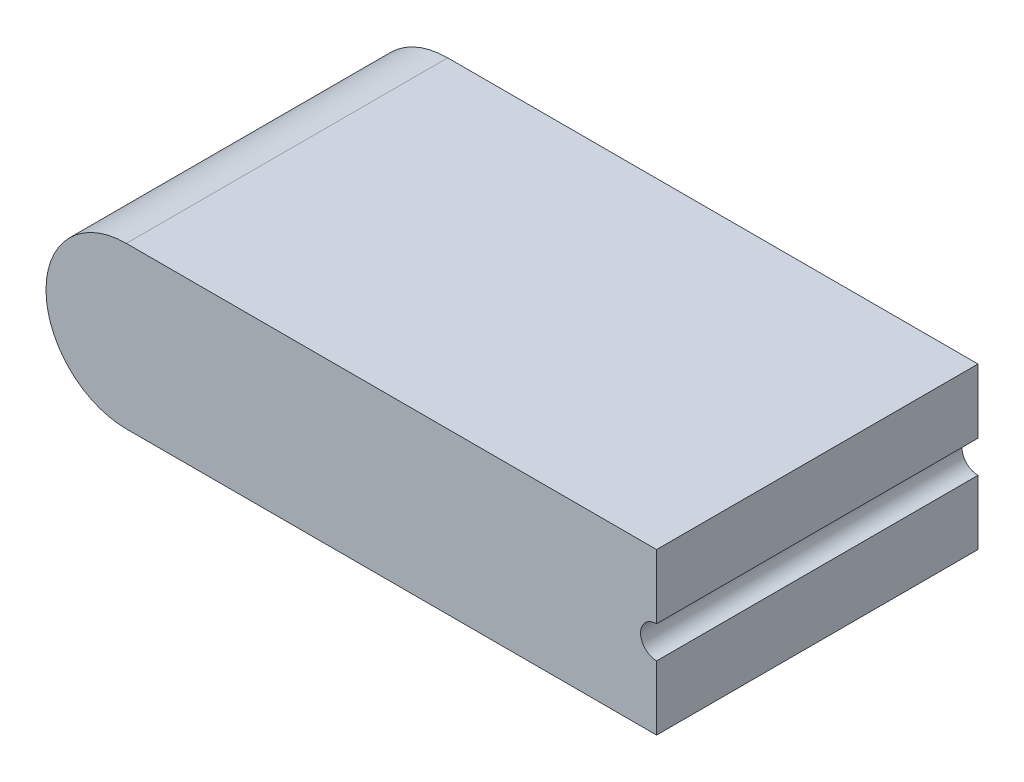
SolidWorks part; units mm, degrees
ref_plane "Front Plane" through (0, 0, 0) normal (0, 0, 1) x (1, 0, 0)
ref_plane "Top Plane" through (0, 0, 0) normal (0, 1, 0) x (1, 0, 0)
ref_plane "Right Plane" through (0, 0, 0) normal (1, 0, 0) x (0, 0, -1)
sketch "Sketch1" plane through (0, 0, 0) normal (0, 1, 0) x (1, 0, 0)
  line L0 (0, 0) -> (6.35, 0)
  line L1 (6.35, 5.08) -> (-3.302, 5.08)
  line L2 (6.35, 0) -> (6.35, 5.08)
  line L3 (-3.302, 5.08) -> (-3.302, 0)
  line L4 (-3.302, 0) -> (0, 0)
extrude "Boss-Extrude1" add sketch "Sketch1" along normal blind 2.54
fillet "Fillet1" radius 1.27 2 edges at (-3.302, 0, -2.54) (-3.302, 2.54, -2.54)
hole_wizard "#97 (0.0059) Diameter Hole2" positions "Sketch7" profile "Sketch6" hole size "#97" standard "ANSI Inch"
sketch "Sketch7" plane through (0, 0, 0) normal (0, 0, 1) x (1, 0, 0)
  line L0 (6.35, 2.54) -> (6.35, 0) construction
  point P0 (6.35, 1.27)
sketch "Sketch6" plane through (6.35, 1.27, 0) normal (1, 0, 0) x (0, -1, 0)
  line L0 (0, 0) -> (0, 25.5526)
  line L1 (0, 25.5526) -> (0.254, 25.4)
  line L2 (0.254, 25.4) -> (0.254, 0)
  line L5 (0.254, 0) -> (0, 0)
  line L10 (0, 25.5526) -> (-0.254, 25.4) construction
  line L11 (0, -6.35) -> (0, 107.95) construction
  dimension "Hole Dia." = 0.508
  dimension "Hole Depth" = 25.4
  dimension "Drill Angle" = 118
